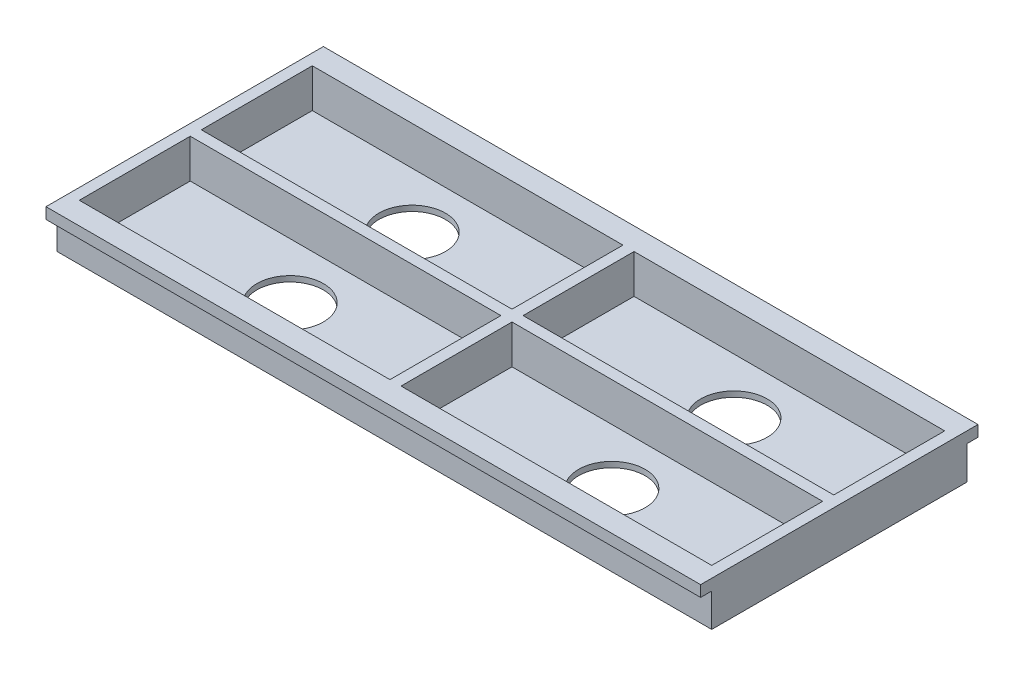
SolidWorks part; units mm, degrees
ref_plane "Front Plane" through (0, 0, 0) normal (0, 0, 1) x (1, 0, 0)
ref_plane "Top Plane" through (0, 0, 0) normal (0, 1, 0) x (1, 0, 0)
ref_plane "Right Plane" through (0, 0, 0) normal (1, 0, 0) x (0, 0, -1)
sketch "Sketch1" plane through (0, 0, 0) normal (0, 1, 0) x (1, 0, 0)
  line L1 (-123.1553, 85.7628) -> (171.8447, 85.7628)
  line L2 (-123.1553, 85.7628) -> (-123.1553, -39.2372)
  line L3 (-123.1553, -39.2372) -> (171.8447, -39.2372)
  line L4 (171.8447, 85.7628) -> (171.8447, -39.2372)
  dimension "D1" = 295
  dimension "D2" = 125
extrude "Boss-Extrude3" add sketch "Sketch1" against normal blind 5 contours L2 L1 L4 L3
sketch "Sketch2" plane through (0, 0, 0) normal (0, 1, 0) x (1, 0, 0)
  line L0 (-123.1553, 85.7628) -> (-123.1553, -39.2372) construction
  line L5 (-123.1553, 80.7628) -> (171.8447, 80.7628)
  line L6 (-123.1553, 80.7628) -> (-123.1553, -34.2372)
  line L7 (-123.1553, -34.2372) -> (171.8447, -34.2372)
  line L8 (171.8447, 80.7628) -> (171.8447, -34.2372)
  line L9 (171.8447, 85.7628) -> (171.8447, -39.2372) construction
  line L10 (-123.1553, 85.7628) -> (171.8447, 85.7628) construction
  line L11 (-123.1553, -39.2372) -> (171.8447, -39.2372) construction
  dimension "D1" = 5
  dimension "D2" = 5
sketch "Sketch3" plane through (0, 0, 0) normal (1, 0, 0) x (0, 0, -1)
  circle A0 centre (23.2628, 25) radius 76
  point P2 (0, 0)
extrude "Boss-Extrude4" add sketch "Sketch2" against normal blind 20
sketch "Sketch4" plane through (0, 0, 0) normal (0, 1, 0) x (1, 0, 0)
  line L0 (-123.1553, 85.7628) -> (171.8447, 85.7628) construction
  line L1 (-118.1553, 75.7628) -> (21.8447, 75.7628)
  line L2 (-118.1553, 75.7628) -> (-118.1553, 25.7628)
  line L3 (-118.1553, 25.7628) -> (21.8447, 25.7628)
  line L4 (21.8447, 75.7628) -> (21.8447, 25.7628)
  line L5 (-123.1553, 85.7628) -> (-123.1553, -39.2372) construction
  line L6 (26.8447, 75.7628) -> (26.8447, 25.7628)
  line L7 (26.8447, 75.7628) -> (166.8447, 75.7628)
  line L8 (166.8447, 75.7628) -> (166.8447, 25.7628)
  line L9 (26.8447, 25.7628) -> (166.8447, 25.7628)
  line L10 (26.8447, 20.7628) -> (26.8447, -29.2372)
  line L11 (26.8447, 20.7628) -> (166.8447, 20.7628)
  line L12 (166.8447, 20.7628) -> (166.8447, -29.2372)
  line L13 (26.8447, -29.2372) -> (166.8447, -29.2372)
  line L14 (-118.1553, 20.7628) -> (-118.1553, -29.2372)
  line L15 (-118.1553, 20.7628) -> (21.8447, 20.7628)
  line L16 (21.8447, 20.7628) -> (21.8447, -29.2372)
  line L17 (-118.1553, -29.2372) -> (21.8447, -29.2372)
  line L18 (-123.1553, -39.2372) -> (171.8447, -39.2372) construction
  point P10 (0, 0)
  point P23 (0, 0)
  point P24 (0, 0)
  point P25 (0, 0)
  dimension "D1" = 140
  dimension "D2" = 50
  dimension "D3" = 10
  dimension "D4" = 5
  dimension "D7" = 10
  dimension "D5" = 2
  dimension "D6" = 2
extrude "Cut-Extrude1" cut sketch "Sketch4" against normal blind 17.5 contours L3 L4 L1 L2
extrude "Cut-Extrude2" cut sketch "Sketch4<3>" against normal blind 17.5
sketch "Sketch4<3>" plane through (0, 0, 0) normal (0, 1, 0) x (1, 0, 0) same geometry as "Sketch4"
sketch "Sketch7" plane through (0, -17.5, 0) normal (0, 1, 0) x (1, 0, 0)
  circle A0 centre (-48.1553, -4.2372) radius 15
  circle A1 centre (96.8447, -4.2372) radius 15
  circle A2 centre (96.8447, 50.7628) radius 15
  circle A3 centre (-48.1553, 50.7628) radius 15
  dimension "D1" = 2
  dimension "D2" = 2
extrude "Cut-Extrude3" cut sketch "Sketch7" against normal blind 31.5
